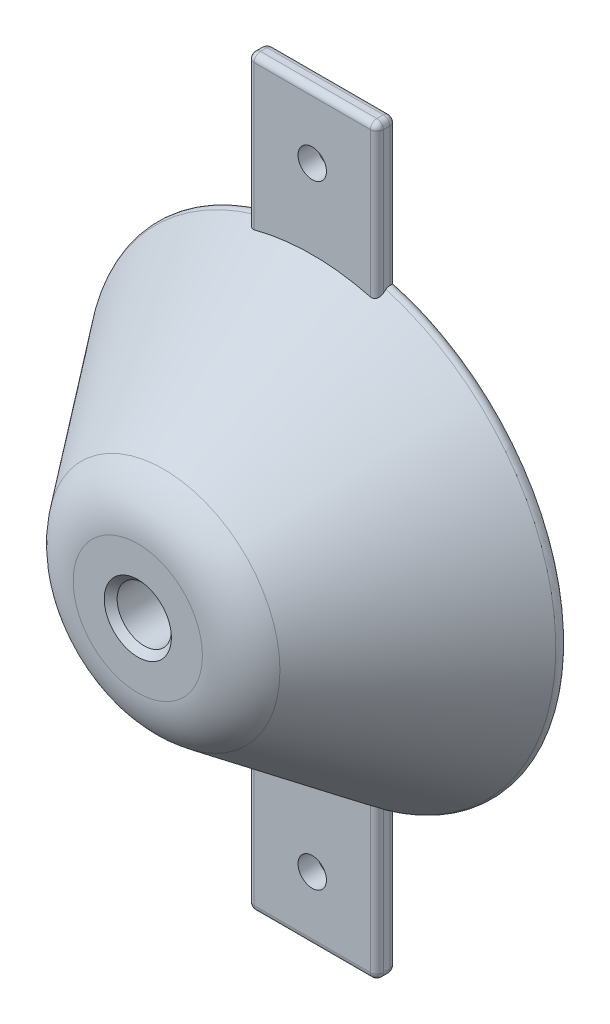
SolidWorks part; units mm, degrees
material "ABS"
ref_plane "Front Plane" through (0, 0, 0) normal (0, 0, 1) x (1, 0, 0)
ref_plane "Top Plane" through (0, 0, 0) normal (0, 1, 0) x (1, 0, 0)
ref_plane "Right Plane" through (0, 0, 0) normal (1, 0, 0) x (0, 0, -1)
sketch "Sketch1" plane through (0, 0, 0) normal (0, 1, 0) x (1, 0, 0)
  line L0 (-37.5, 0) -> (0, 0)
  line L1 (0, 0) -> (0, -30)
  line L2 (0, -30) -> (-15, -30)
  line L3 (-15, -30) -> (-37.5, 0)
  line L4 (0, 0) -> (0, -30) construction
  dimension "D1" = 37.5
  dimension "D2" = 15
  dimension "D3" = 30
revolve "Revolve1" add sketch "Sketch1" angle 360 about L4
fillet "Fillet1" radius 1 1 edges at (-37.5, 0, 0)
fillet "Fillet2" radius 10 1 edges at (-15, 0, 30)
sketch "Sketch4" plane through (0, 0, 0) normal (0, 0, -1) x (-1, 0, 0)
  line L1 (10, 57.5) -> (-10, 57.5)
  line L2 (10, 57.5) -> (10, -57.5)
  line L3 (10, -57.5) -> (-10, -57.5)
  line L4 (-10, 57.5) -> (-10, -57.5)
  line L5 (10, 57.5) -> (-10, -57.5) construction
  line L6 (10, -57.5) -> (-10, 57.5) construction
  point P0 (0, 0)
  dimension "D1" = 115
  dimension "D2" = 20
extrude "Boss-Extrude1" add sketch "Sketch4" against normal blind 3
sketch "Sketch2" plane through (0, 0, 30) normal (0, 0, 1) x (1, 0, 0)
  circle A0 centre (0, 0) radius 4.2
  dimension "D1" = 8.4
extrude "Cut-Extrude1" cut sketch "Sketch2" against normal through all
sketch "Sketch3" plane through (0, 0, 0) normal (0, 0, -1) x (-1, 0, 0)
  line L1 (-8.3, 0) -> (-4.15, -7.188)
  line L2 (-4.15, -7.188) -> (4.15, -7.188)
  line L3 (4.15, -7.188) -> (8.3, 0)
  line L4 (8.3, 0) -> (4.15, 7.188)
  line L5 (4.15, 7.188) -> (-4.15, 7.188)
  line L6 (-4.15, 7.188) -> (-8.3, 0)
  circle A0 centre (0, 0) radius 7.188 construction
  dimension "D1" = 14.376
extrude "Cut-Extrude2" cut sketch "Sketch3" along normal through all from offset 8 offset against normal yes
chamfer "Chamfer1" distance 1 angle 45 8 edges at (4.2, 0, 30) (-6.225, 3.594, 0) (-6.225, -3.594, 0) (0, -7.188, 0) (6.225, -3.594, 0) (6.225, 3.594, 0) (0, 7.188, 0) (-4.2, 0, 8)
fillet "Fillet4" radius 1 16 edges at (-10, -57.5, 1.5) (0, -57.5, 3) (10, -57.5, 1.5) (0, -57.5, 0) (10, -45.7812, 0) (10, -45.6509, 3) (-10, -45.6509, 3) (-10, -45.7812, 0) (10, 57.5, 1.5) (0, 57.5, 3) (-10, 57.5, 1.5) (0, 57.5, 0) (-10, 45.7812, 0) (-10, 45.6509, 3) (10, 45.6509, 3) (10, 45.7812, 0)
sketch "Sketch5" plane through (0, 0, 3) normal (0, 0, 1) x (1, 0, 0)
  line L0 (0, 47.5) -> (0, -47.5) construction
  circle A0 centre (0, 47.5) radius 2.2
  circle A1 centre (0, -47.5) radius 2.2
  dimension "D1" = 4.4
  dimension "D2" = 95
extrude "Cut-Extrude3" cut sketch "Sketch5" against normal through all
